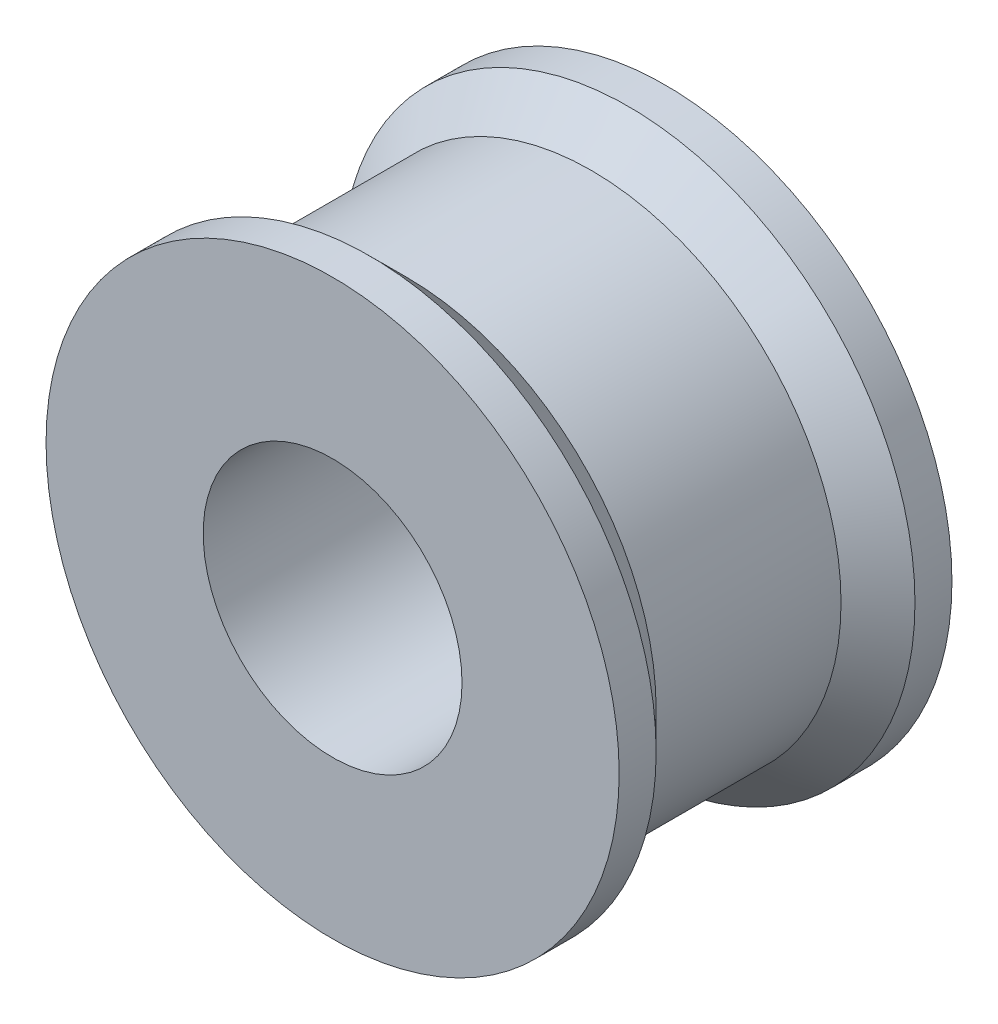
SolidWorks part; units mm, degrees
ref_plane "Front Plane" through (0, 0, 0) normal (0, 0, 1) x (1, 0, 0)
ref_plane "Top Plane" through (0, 0, 0) normal (0, 1, 0) x (1, 0, 0)
ref_plane "Right Plane" through (0, 0, 0) normal (1, 0, 0) x (0, 0, -1)
sketch "Sketch1" plane through (0, 0, 0) normal (0, 0, 1) x (1, 0, 0)
  circle A0 centre (0, 0) radius 3.5
  circle A1 centre (0, 0) radius 7.75
  dimension "D1" = 7
  dimension "D2" = 15.5
extrude "Boss-Extrude1" add sketch "Sketch1" along normal blind 1
sketch "Sketch2" plane through (0, 0, 1) normal (0, 0, 1) x (1, 0, 0)
  circle A0 centre (0, 0) radius 3.5
  circle A1 centre (0, 0) radius 6.75
  circle A2 centre (0, 0) radius 3.5 construction
  dimension "D1" = 13.5
extrude "Boss-Extrude2" add sketch "Sketch2" along normal blind 3.5
chamfer "Chamfer1" distance 1 angle 45 1 edges at (6.75, 0, 1)
mirror "Mirror5" about plane through (0, 0, 4.5) normal (0, 0, 1) of bodies 102
